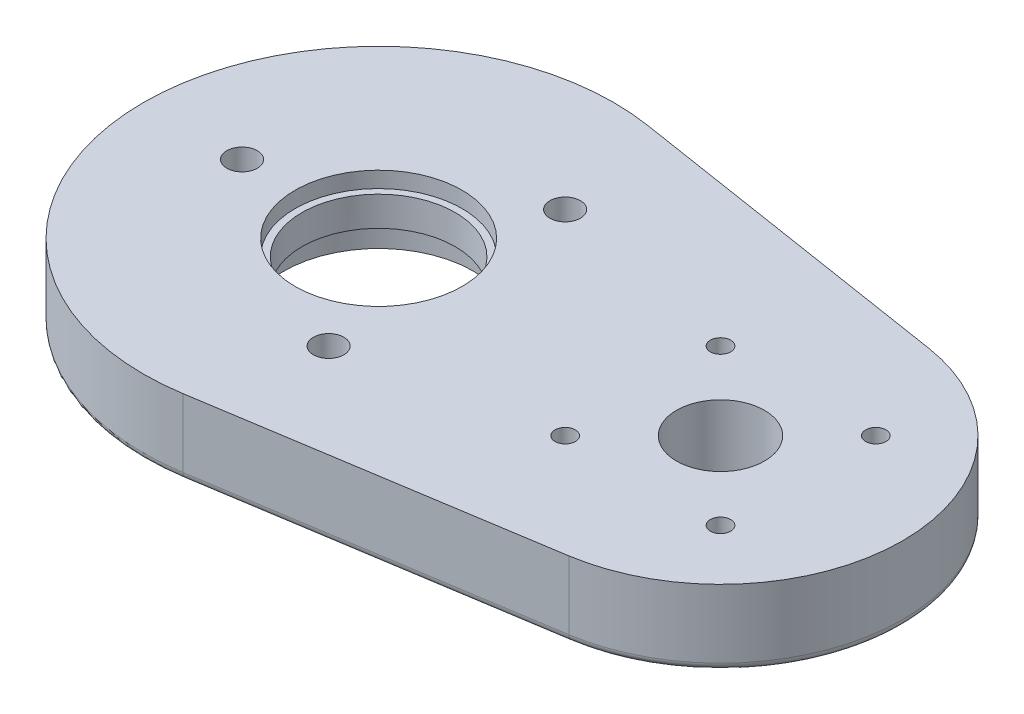
SolidWorks part; units mm, degrees
ref_plane "Front Plane" through (0, 0, 0) normal (0, 0, 1) x (1, 0, 0)
ref_plane "Top Plane" through (0, 0, 0) normal (0, 1, 0) x (1, 0, 0)
ref_plane "Right Plane" through (0, 0, 0) normal (1, 0, 0) x (0, 0, -1)
sketch "Sketch1" plane through (0, 0, 0) normal (0, 1, 0) x (1, 0, 0)
  line L0 (-51.1101, 38.892) -> (4.735, 30.11)
  line L1 (-51.1101, -38.892) -> (4.735, -30.11)
  arc A0 (4.735, -30.11) -> (4.735, 30.11) centre (0, 0) ccw
  arc A1 (-51.1101, 38.892) -> (-51.1101, -38.892) centre (-57.2262, 0) ccw
  dimension "D1" = 60.96
  dimension "D2" = 78.74
  dimension "D3" = 57.2262
extrude "Boss-Extrude1" add sketch "Sketch1" along normal blind 12.7
sketch "Sketch2" plane through (0, 12.7, 0) normal (0, 1, 0) x (1, 0, 0)
  circle A0 centre (-57.2262, 0) radius 12.827
  circle A1 centre (0, 0) radius 7.366
  dimension "D1" = 14.732
  dimension "D2" = 25.654
extrude "Cut-Extrude1" cut sketch "Sketch2" against normal through all
hole_wizard "CBORE for #10 Socket Head Cap Screw1" positions "Sketch10" profile "Sketch12" counterbore size "#10" standard "ANSI Inch" end condition through all
sketch "Sketch10" plane through (0, 0, 0) normal (0, -1, 0) x (-1, 0, 0)
  line L10 (80.0862, 0) -> (45.7962, 19.7973) construction
  line L11 (45.7962, 19.7973) -> (45.7962, -19.7973) construction
  line L12 (45.7962, -19.7973) -> (80.0862, 0) construction
  line L16 (0, 0) -> (57.2262, 0) construction
  circle A0 centre (57.2262, 0) radius 11.43 construction
  point P55 (45.7962, 19.7973)
  point P58 (45.7962, -19.7973)
  point P61 (80.0862, 0)
  dimension "D1" = 22.86
sketch "Sketch12" plane through (-80.0862, 0, 0) normal (1, 0, 0) x (0, 0, -1)
  line L0 (0, 0) -> (0, 12.7)
  line L1 (0, 12.7) -> (2.5527, 12.7)
  line L3 (2.5527, 12.7) -> (2.5527, 4.826)
  line L4 (4.7625, 4.826) -> (2.5527, 4.826)
  line L5 (4.7625, 4.826) -> (4.7625, 0.635)
  line L6 (4.7625, 0.635) -> (5.3975, 0)
  line L7 (5.3975, 0) -> (0, 0)
  line L8 (-4.7625, 0.635) -> (-5.3975, 0) construction
  line L11 (0, -6.35) -> (0, 107.95) construction
  dimension "Thru Hole Dia." = 5.1054
  dimension "Thru Hole Depth" = 12.7
  dimension "C'Bore Dia." = 9.525
  dimension "C'Bore Depth" = 4.826
  dimension "Near C'Sink Dia." = 10.795
  dimension "Near C'Sink Angle" = 90
hole_wizard "CBORE for M3 SHCS1" positions "Sketch15" profile "Sketch16" counterbore size "M3" standard "ANSI Metric" end condition through all
sketch "Sketch15" plane through (0, 0, 0) normal (0, -1, 0) x (-1, 0, 0)
  line L1 (-13, -13) -> (13, -13) construction
  line L2 (-13, -13) -> (-13, 13) construction
  line L3 (-13, 13) -> (13, 13) construction
  line L4 (13, -13) -> (13, 13) construction
  line L5 (-13, -13) -> (13, 13) construction
  line L6 (-13, 13) -> (13, -13) construction
  circle A0 centre (57.2262, 0) radius 12.827 construction
  point P1 (13, 13)
  point P42 (-13, -13)
  point P43 (-13, 13)
  point P44 (13, -13)
  dimension "D1" = 26
  dimension "D2" = 44.2262
  dimension "D3" = 13
sketch "Sketch16" plane through (-13, 0, -13) normal (1, 0, 0) x (0, 0, -1)
  line L0 (0, 0) -> (0, 12.7)
  line L1 (0, 12.7) -> (1.7, 12.7)
  line L3 (1.7, 12.7) -> (1.7, 3)
  line L4 (3.25, 3) -> (1.7, 3)
  line L5 (3.25, 3) -> (3.25, 0.75)
  line L6 (3.25, 0.75) -> (4, 0)
  line L7 (4, 0) -> (0, 0)
  line L8 (-3.25, 0.75) -> (-4, 0) construction
  line L11 (0, -6.35) -> (0, 107.95) construction
  dimension "Thru Hole Dia." = 3.4
  dimension "Thru Hole Depth" = 12.7
  dimension "C'Bore Dia." = 6.5
  dimension "C'Bore Depth" = 3
  dimension "Near C'Sink Dia." = 8
  dimension "Near C'Sink Angle" = 90
fillet "Fillet1" radius 1.27 5 edges at (-96.5962, 0, 0) (-23.1876, 0, -34.501) (30.48, 0, 0) (0, 0, 7.366) (-23.1876, 0, 34.501)
sketch "Sketch13" plane through (0, 0, 0) normal (0, -1, 0) x (1, 0, 0)
  circle A0 centre (-57.2262, 0) radius 15.875
  circle A1 centre (-57.2262, 0) radius 12.827
  dimension "D1" = 31.75
extrude "bearing_pocket" cut sketch "Sketch13" against normal blind 5.08
sketch "Sketch14" plane through (0, 12.7, 0) normal (0, 1, 0) x (1, 0, 0)
  circle A0 centre (-57.2262, 0) radius 13.97
  circle A1 centre (-57.2262, 0) radius 12.827
  dimension "D1" = 27.94
  dimension "D2" = 25.654
extrude "Cut-Extrude3" cut sketch "Sketch14" against normal blind 2.667
